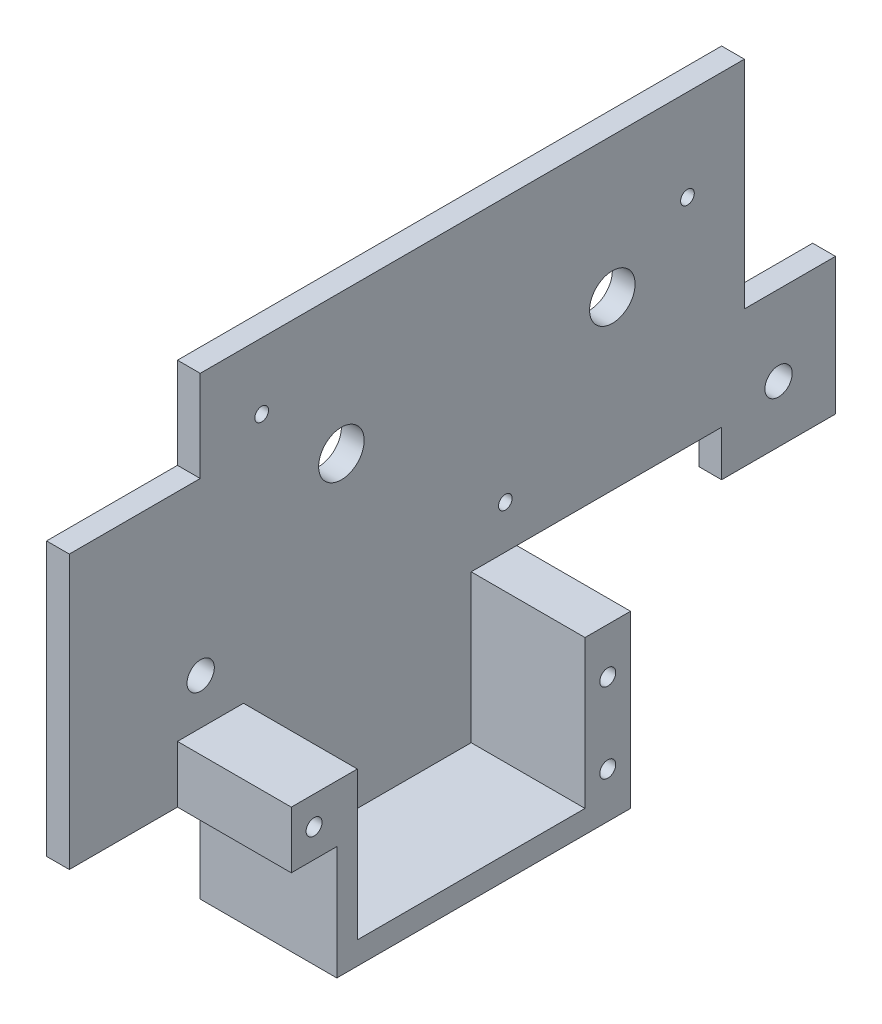
SolidWorks part; units mm, degrees
ref_plane "前视基准面" through (0, 0, 0) normal (0, 0, 1) x (1, 0, 0)
ref_plane "上视基准面" through (0, 0, 0) normal (0, 1, 0) x (1, 0, 0)
ref_plane "右视基准面" through (0, 0, 0) normal (1, 0, 0) x (0, 0, -1)
other "Configuration Table"
sketch "草图1" plane through (0, 0, 0) normal (1, 0, 0) x (0, 0, -1)
  line L5 (0, 0) -> (-28, 0)
  line L6 (0, 0) -> (0, -13.5)
  line L7 (0, -13.5) -> (-28, -13.5)
  line L8 (-28, 0) -> (-28, -13.5)
  dimension "D1" = 28
  dimension "D2" = 13.5
extrude "凸台-拉伸1" add sketch "草图1" along normal blind 1 contours L7 L8 L5 L6 | L8 L7 L6 L5 region at (0, -6.75, 14)
sketch "草图2" plane through (1, 0, 0) normal (1, 0, 0) x (0, 0, -1)
  line L0 (0, 0) -> (0, -13.5) construction
  line L1 (0, 0) -> (-28, 0) construction
  line L2 (0, -13.5) -> (-28, -13.5) construction
  line L3 (0, -10.5) -> (5, -10.5)
  line L4 (0, -10.5) -> (0, -15.5)
  line L5 (0, -15.5) -> (5, -15.5)
  line L6 (5, -10.5) -> (5, -15.5)
  line L7 (-28, 0) -> (-28, -13.5) construction
  line L8 (-28, -9.5) -> (-10, -9.5)
  line L9 (-28, -9.5) -> (-28, -13.5)
  line L10 (-28, -13.5) -> (-10, -13.5)
  line L11 (-10, -9.5) -> (-10, -13.5)
  line L13 (0, -9.5) -> (5, -9.5)
  line L14 (0, -9.5) -> (0, -10.5)
  line L15 (0, -10.5) -> (5, -10.5)
  line L16 (5, -9.5) -> (5, -10.5)
  circle A0 centre (-1.5, -4) radius 0.3
  circle A2 centre (-20.2, -2.9) radius 0.3
  circle A3 centre (-9.5, -11.6) radius 0.3
  circle A5 centre (2.5, -13) radius 0.6
  point P22 (0, 0)
  point P27 (2.5, -10.5)
  point P29 (5, -13)
  line M4 (-28, -13.5) -> (0, -13.5)
  line M5 (0, -13.5) -> (0, 0)
  dimension "D2" = 0.6
  dimension "D11" = 18.7
  dimension "D9" = 1.2
  dimension "D1" = 1.5
  dimension "D3" = 4
  dimension "D4" = 5
  dimension "D5" = 3
  dimension "D6" = 5
  dimension "D7" = 4
  dimension "D8" = 18
  dimension "D10" = 8
  dimension "D12" = 1
  dimension "D13" = 1.1
  dimension "D14" = 7.6
extrude "切除-拉伸1" cut sketch "草图2" against normal through all contours A0 | A3 | A2
extrude "凸台-拉伸2" add sketch "草图2<3>" against normal up to surface (1 mm away) contours L16 L13 L3 M5 | L4 M4 | L4 L5 L6 L3 region at (1, -10, -2.5) up to face at (0, -4, 1.2)
sketch "草图2<3>" plane through (1, 0, 0) normal (1, 0, 0) x (0, 0, -1) same geometry as "草图2"
extrude "切除-拉伸2" cut sketch "草图2<4>" against normal through all contours A5
sketch "草图2<4>" plane through (1, 0, 0) normal (1, 0, 0) x (0, 0, -1) same geometry as "草图2"
sketch "草图3" plane through (1, 0, 0) normal (1, 0, 0) x (0, 0, -1)
  line L2 (0, 0) -> (-28, 0) construction
  circle A0 centre (-4.8, -6.15) radius 1
  circle A1 centre (-16.7, -6.15) radius 1
  circle A2 centre (-1.5, -4) radius 0.3 construction
  point P4 (0, 0)
  dimension "D1" = 2
  dimension "D2" = 2
  dimension "D3" = 11.9
  dimension "D4" = 3.3
  dimension "D5" = 6.15
extrude "切除-拉伸3" cut sketch "草图3" against normal through all contours A1 | A0
sketch "草图4" plane through (1, 0, 0) normal (1, 0, 0) x (0, 0, -1)
  line L0 (0, 0) -> (-28, 0) construction
  line L1 (-22.9, 0) -> (-29.9, 0)
  line L2 (-22.9, 0) -> (-22.9, -4)
  line L3 (-22.9, -4) -> (-29.9, -4)
  line L4 (-29.9, 0) -> (-29.9, -4)
  dimension "D2" = 7
  dimension "D3" = 4
extrude "切除-拉伸4" cut sketch "草图4" against normal blind 1.5
sketch "草图5" plane through (0, 0, 0) normal (-1, 0, 0) x (0, 0, 1)
  circle A0 centre (22.8807, -11.5) radius 0.6
  dimension "D1" = 1.2
extrude "切除-拉伸5" cut sketch "草图5" against normal through all
sketch "草图6" plane through (1, 0, 0) normal (1, 0, 0) x (0, 0, -1)
  line L0 (0, -9.5) -> (5, -9.5) construction
  line L1 (0, 0) -> (1, 0)
  line L2 (0, 0) -> (0, -9.5)
  line L3 (0, -9.5) -> (1, -9.5)
  line L4 (1, 0) -> (1, -9.5)
  point P6 (0, 0)
  dimension "D1" = 1
extrude "凸台-拉伸3" add sketch "草图6" against normal up to surface (1 mm away) contours L4 L3 L2 L1 up to face at (0, -11.5, 23.4807)
sketch "草图7" plane through (1, 0, 0) normal (1, 0, 0) x (0, 0, -1)
  line L0 (1, 0) -> (-22.9, 0) construction
  line L1 (-11, -10) -> (-21, -10)
  line L2 (-11, -10) -> (-11, -20)
  line L3 (-11, -20) -> (-21, -20)
  line L4 (-21, -10) -> (-21, -20)
  line L15 (0, -13.5) -> (-28, -13.5) construction
  line L20 (-11, -13.5) -> (-9, -13.5)
  line L21 (-11, -13.5) -> (-11, -20)
  line L26 (-11, -20) -> (-9, -20)
  line L27 (-9, -13.5) -> (-9, -20)
  line L33 (-21, -20) -> (-9, -20)
  line L34 (-21, -20) -> (-21, -21)
  line L35 (-21, -21) -> (-9, -21)
  line L36 (-9, -20) -> (-9, -21)
  line L37 (-21, -21) -> (-21.9, -21)
  line L38 (-21, -21) -> (-21, -13.5)
  line L39 (-21, -13.5) -> (-21.9, -13.5)
  line L40 (-21.9, -21) -> (-21.9, -13.5)
  line L41 (-21.9, -13.5) -> (-23.9, -13.5)
  line L42 (-21.9, -13.5) -> (-21.9, -16)
  line L43 (-21.9, -16) -> (-23.9, -16)
  line L44 (-23.9, -13.5) -> (-23.9, -16)
  circle A0 centre (-10, -19) radius 0.35
  circle A1 centre (-10, -15.5) radius 0.35
  circle A2 centre (-22.9, -14.75) radius 0.35
  point P26 (-23.9, -14.75)
  point P27 (-22.9, -16)
  point P28 (-10, -13.5)
  line M7 (-28, -13.5) -> (0, -13.5)
  dimension "D9" = 0.7
  dimension "D1" = 10
  dimension "D2" = 10
  dimension "D3" = 11
  dimension "D4" = 2
  dimension "D5" = 1
  dimension "D6" = 0.9
  dimension "D7" = 2.5
  dimension "D8" = 2
  dimension "D10" = 2
  dimension "D11" = 2
extrude "凸台-拉伸4" add sketch "草图7" against normal up to surface (1 mm away) contours L44 L43 L40 M7 | L40 L37 L34 L4 M7 | L4 L3 L2 M7 | L36 L26 L3 L34 L35 | L27 L2 L26 M7 region at (1, -16.7185, 10) region at (1, -16.75, 16) region at (1, -17.25, 21.45) region at (1, -20.5, 15) region at (1, -14.75, 21.932) up to face at (0, -11.5, 23.4807)
extrude "凸台-拉伸5" add sketch "草图7<3>" along normal blind 5 from surface contours L40 L37 L34 L4 M7 | L44 L43 L40 A2 M7 | L36 L26 L3 L34 L35 | L27 L2 L26 A1 A0 M7 region at (1, -16.7185, 10) region at (1, -17.25, 21.45) region at (1, -20.5, 15) region at (1, -14.75, 21.932) starting at face at (1, -11.5, 23.4807)
sketch "草图7<3>" plane through (1, 0, 0) normal (1, 0, 0) x (0, 0, -1) same geometry as "草图7"
sketch "草图8" plane through (1, 0, 0) normal (1, 0, 0) x (0, 0, -1)
  line L7 (-23.9, -16) -> (-28.65, -16)
  line L8 (-23.9, -16) -> (-23.9, -13.5)
  line L9 (-23.9, -13.5) -> (-28.65, -13.5)
  line L10 (-28.65, -16) -> (-28.65, -13.5)
  line L11 (-28, -4) -> (-28.65, -4)
  line L12 (-28, -4) -> (-28, -13.5)
  line L13 (-28, -13.5) -> (-28.65, -13.5)
  line L14 (-28.65, -4) -> (-28.65, -13.5)
  point P0 (-24.525, -15.8467)
  point P4 (-20.7868, -17.516)
  point P17 (-21, -18.7085)
  line M15 (-28, -4) -> (-28, -13.5)
  line M16 (-28, -13.5) -> (-23.9, -13.5)
  dimension "D1" = 0.65
extrude "凸台-拉伸6" add sketch "草图8" against normal up to surface (1 mm away) contours L11 L14 L9 M15 | L10 L7 L8 L9 M16 region at (1, -14.75, 26.275) region at (1, -8.75, 28.325) up to face at (0, -11.5, 23.4807)
